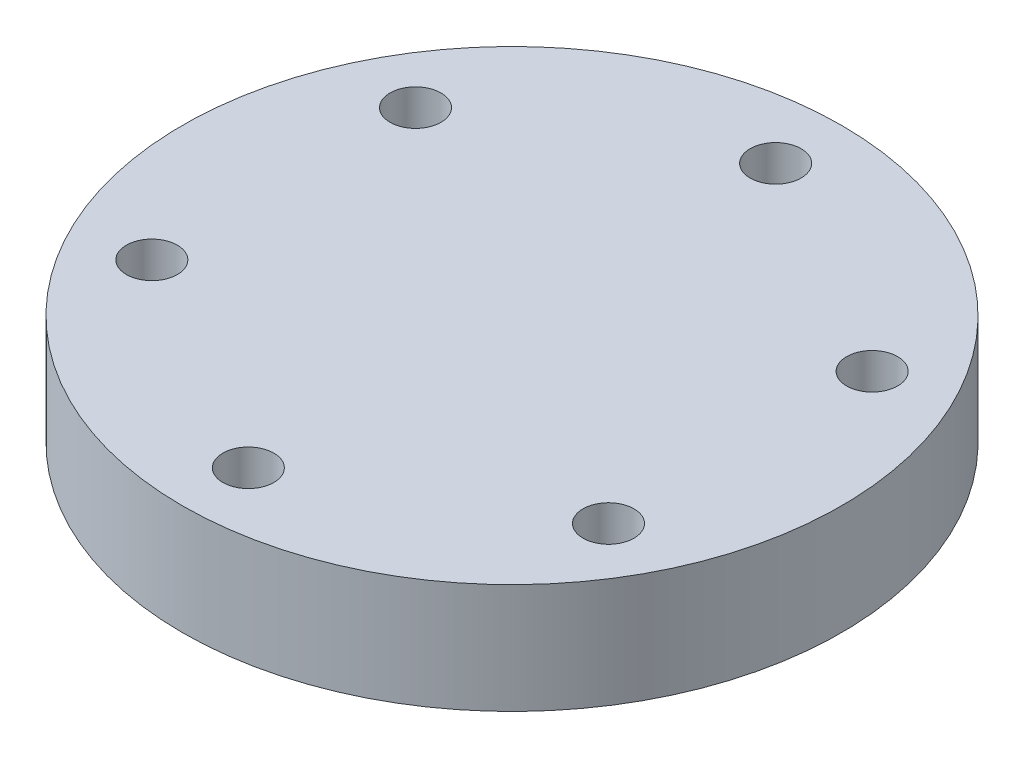
SolidWorks part; units mm, degrees
ref_plane "Front Plane" through (0, 0, 0) normal (0, 0, 1) x (1, 0, 0)
ref_plane "Top Plane" through (0, 0, 0) normal (0, 1, 0) x (1, 0, 0)
ref_plane "Right Plane" through (0, 0, 0) normal (1, 0, 0) x (0, 0, -1)
ref_axis "Y Axis" through (0, 6.6675, 0) along (0, -1, 0)
sketch "outer" plane through (0, 0, 0) normal (0, 1, 0) x (1, 0, 0)
  circle A0 centre (0, 0) radius 19.05
  dimension "D1" = 38.1
extrude "Body" add sketch "outer" along normal blind 6.35
sketch "inner" plane through (0, 0, 0) normal (0, 1, 0) x (1, 0, 0)
  circle A0 centre (0, 0) radius 11.6205
  dimension "D1" = 23.241
extrude "Pocket" cut sketch "inner" along normal blind 3.175
sketch "Screw Position" plane through (0, 0, 0) normal (0, 1, 0) x (1, 0, 0)
  point P0 (0, 15.24)
hole_wizard "#32 (0.116) Diameter Hole1" positions "Sketch7" profile "Sketch8" hole size "#32" standard "ANSI Inch" end condition through all
sketch "Sketch7" plane through (0, 6.35, 0) normal (0, 1, 0) x (1, 0, 0)
  point P0 (0, 15.24)
sketch "Sketch8" plane through (0, 6.35, -15.24) normal (1, 0, 0) x (0, 0, 1)
  line L0 (0, 0) -> (0, 6.35)
  line L1 (0, 6.35) -> (1.4732, 6.35)
  line L2 (1.4732, 6.35) -> (1.4732, 0)
  line L5 (1.4732, 0) -> (0, 0)
  line L11 (0, -6.35) -> (0, 107.95) construction
  dimension "Thru Hole Dia." = 2.9464
  dimension "Thru Hole Depth" = 6.35
pattern_circular "Screw Holes" count 6 over 360 about axis through (0, 6.6675, 0) along (0, -1, 0) of "#32 (0.116) Diameter Hole1"
equation "\"outer_d\"= 3 / 2in"
equation "\"top_h\"= 1 / 4in"
equation "\"screw_r\"= 0.6in"
equation "\"inner_d\"= 0.915in"
equation "\"inner_h\"= 1 / 8in"
equation "\"D1@outer\" = \"outer_d\""
equation "\"D1@Body\" = \"top_h\""
equation "\"D1@inner\"=\"inner_d\""
equation "\"D1@Pocket\" = \"inner_h\""
equation "\"D1@Screw Position\"=\"screw_r\""
